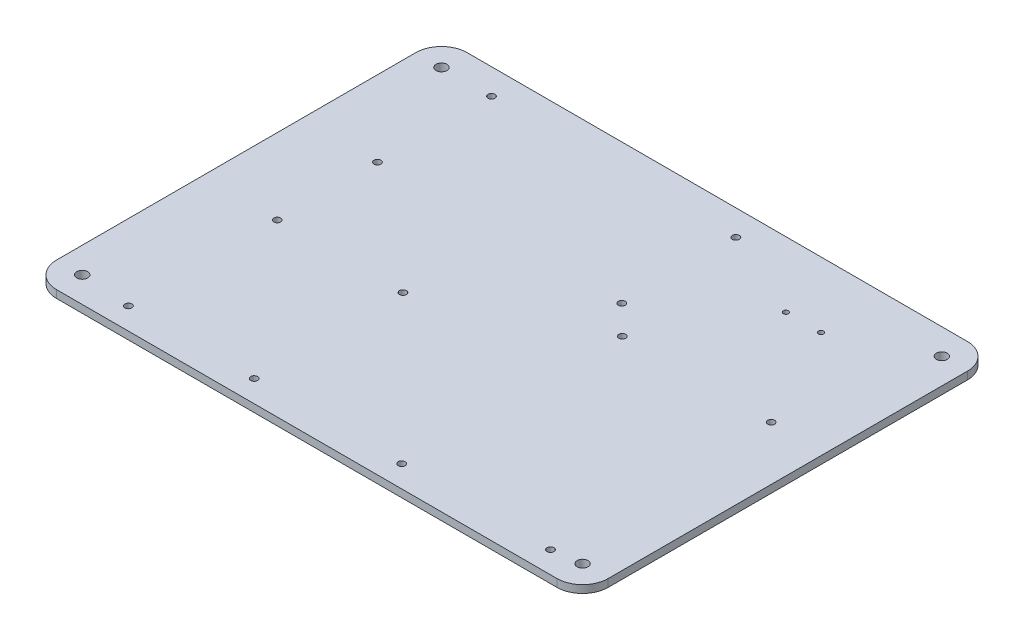
SolidWorks part; units mm, degrees
material "PP Copolymer"
ref_plane "Front Plane" through (0, 0, 0) normal (0, 0, 1) x (1, 0, 0)
ref_plane "Top Plane" through (0, 0, 0) normal (0, 1, 0) x (1, 0, 0)
ref_plane "Right Plane" through (0, 0, 0) normal (1, 0, 0) x (0, 0, -1)
sketch "Sketch1" plane through (0, 210, 0) normal (0, 1, 0) x (1, 0, 0)
  line L0 (-107.5, 102.5) -> (-107.5, -102.5) construction
  line L1 (-107.5, 80) -> (107.5, 80)
  line L2 (-107.5, 80) -> (-107.5, -80)
  line L3 (-107.5, -80) -> (107.5, -80)
  line L4 (107.5, 80) -> (107.5, -80)
  line L5 (107.5, 122.5) -> (107.5, -227.5) construction
  line L6 (107.5, 102.5) -> (107.5, -102.5) construction
  line L7 (-107.5, 80) -> (-107.5, 102.5) construction
  line L8 (-107.5, -80) -> (-107.5, -102.5) construction
  dimension "D1" = 160
extrude "Boss-Extrude1" add sketch "Sketch1" along normal blind 3
sketch "Sketch2" plane through (0, 213, 0) normal (0, 1, 0) x (1, 0, 0)
  line L0 (-107.5, -80) -> (107.5, -80) construction
  line L1 (-78.5, 10) -> (-28.5, 10) construction
  line L2 (-81.5, 7) -> (-81.5, -72) construction
  line L3 (-78.5, -75) -> (-28.5, -75) construction
  line L4 (-25.5, 7) -> (-25.5, -72) construction
  line L5 (-107.5, 80) -> (-107.5, -80) construction
  line L6 (107.5, 80) -> (-107.5, 80) construction
  line L7 (-78, -13.5) -> (-29, -13.5) construction
  line L8 (-78, -13.5) -> (-78, -71.5) construction
  line L9 (-78, -71.5) -> (-29, -71.5) construction
  line L10 (-29, -13.5) -> (-29, -71.5) construction
  line L11 (28.5, 14.5) -> (86.5, 14.5) construction
  line L12 (28.5, 14.5) -> (28.5, -71.5) construction
  line L13 (28.5, -71.5) -> (86.5, -71.5) construction
  line L14 (86.5, 14.5) -> (86.5, -71.5) construction
  line L15 (-78, 70) -> (17.25, 70) construction
  line L16 (-78, 70) -> (-78, 25.55) construction
  line L17 (-78, 25.55) -> (17.25, 25.55) construction
  line L18 (17.25, 70) -> (17.25, 25.55) construction
  line L19 (107.5, -80) -> (107.5, 80) construction
  line L20 (-97.5, 70) -> (97.5, 70) construction
  line L21 (-97.5, 70) -> (-97.5, -70) construction
  line L22 (-97.5, -70) -> (97.5, -70) construction
  line L23 (97.5, 70) -> (97.5, -70) construction
  arc A0 (-81.5, -72) -> (-78.5, -75) centre (-78.5, -72) ccw construction
  arc A1 (-28.5, -75) -> (-25.5, -72) centre (-28.5, -72) ccw construction
  arc A2 (-28.5, 10) -> (-25.5, 7) centre (-28.5, 7) cw construction
  arc A3 (-78.5, 10) -> (-81.5, 7) centre (-78.5, 7) ccw construction
  circle A4 centre (-78, -13.5) radius 1.35
  circle A5 centre (-29, -13.5) radius 1.35
  circle A6 centre (-29, -71.5) radius 1.35
  circle A7 centre (-78, -71.5) radius 1.35
  circle A8 centre (86.5, 14.5) radius 1.35
  circle A9 centre (86.5, -71.5) radius 1.35
  circle A10 centre (28.5, -71.5) radius 1.35
  circle A11 centre (28.5, 14.5) radius 1.35
  circle A12 centre (-78, 70) radius 1.35
  circle A13 centre (-78, 25.55) radius 1.35
  circle A14 centre (17.25, 25.55) radius 1.35
  circle A15 centre (17.25, 70) radius 1.35
  circle A16 centre (52.25, 54.5) radius 1
  circle A17 centre (65.95, 54.5) radius 1
  circle A18 centre (97.5, -70) radius 2.125
  circle A19 centre (97.5, 70) radius 2.125
  circle A20 centre (-97.5, 70) radius 2.125
  circle A21 centre (-97.5, -70) radius 2.125
  point P11 (-81.5, -75)
  point P16 (-25.5, 10)
  point P19 (-81.5, 10)
  dimension "D5" = 3
  dimension "D8" = 2.7
  dimension "D14" = 2.7
  dimension "D17" = 2.7
  dimension "D19" = 2
  dimension "D20" = 11.7
  dimension "D27" = 4.25
  dimension "D1" = 85
  dimension "D2" = 56
  dimension "D3" = 5
  dimension "D4" = 26
  dimension "D6" = 58
  dimension "D7" = 49
  dimension "D9" = 3.5
  dimension "D10" = 3.5
  dimension "D11" = 86
  dimension "D12" = 58
  dimension "D13" = 54
  dimension "D15" = 95.25
  dimension "D16" = 44.45
  dimension "D18" = 10
  dimension "D21" = 40
  dimension "D22" = 35
  dimension "D23" = 10
  dimension "D24" = 10
  dimension "D25" = 10
  dimension "D26" = 10
extrude "Cut-Extrude1" cut sketch "Sketch2" against normal through all
fillet "Fillet1" radius 10 4 edges at (-107.5, 211.5, 80) (107.5, 211.5, 80) (107.5, 211.5, -80) (-107.5, 211.5, -80)
